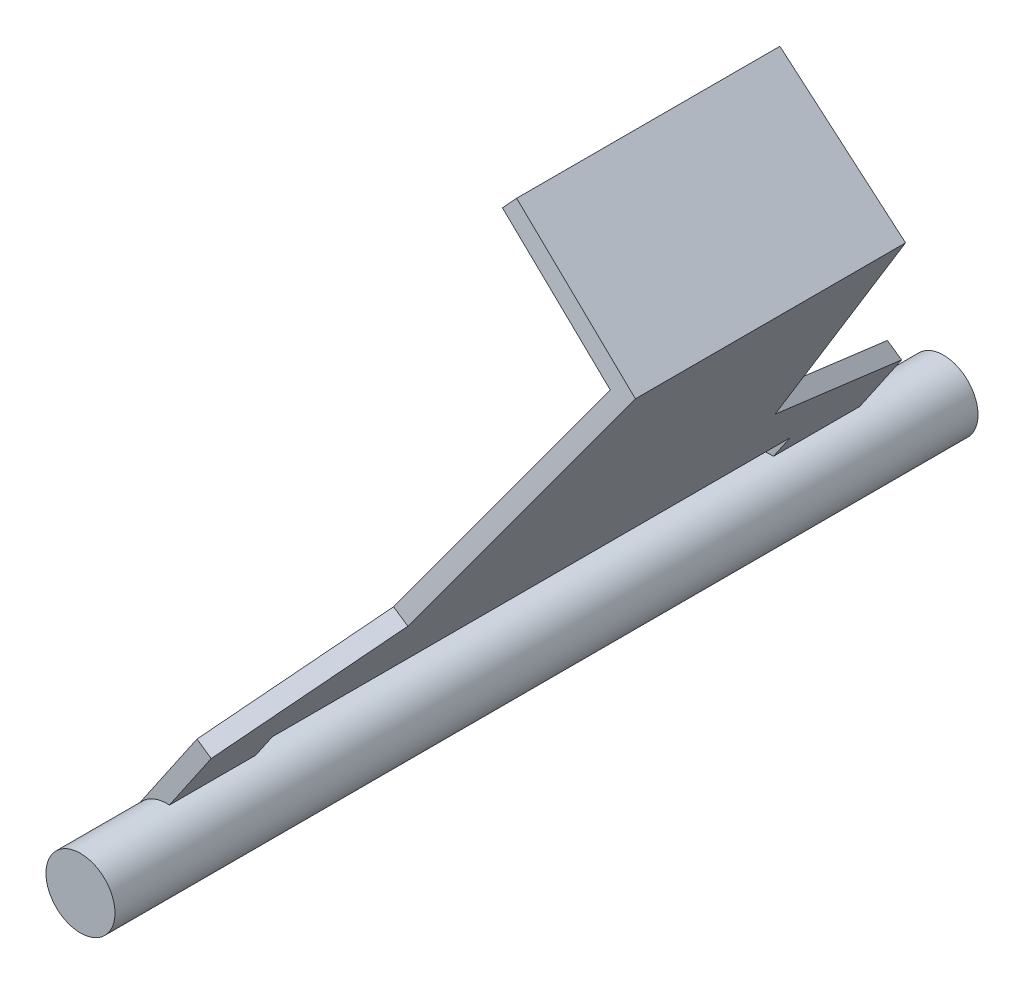
SolidWorks part; units mm, degrees
ref_plane "前视基准面" through (0, 0, 0) normal (0, 0, 1) x (1, 0, 0)
ref_plane "上视基准面" through (0, 0, 0) normal (0, 1, 0) x (1, 0, 0)
ref_plane "右视基准面" through (0, 0, 0) normal (1, 0, 0) x (0, 0, -1)
sketch "草图1" plane through (0, 0, 0) normal (0, 0, 1) x (1, 0, 0)
  line L0 (-3.3033, 2.2558) -> (27.3198, 47.099)
  line L1 (27.3198, 47.099) -> (14.4498, 58.7751)
  line L2 (0.3019, 3.9886) -> (29.9538, 47.4097)
  line L3 (29.9538, 47.4097) -> (15.7937, 60.2564)
  line L4 (15.7937, 60.2564) -> (14.4498, 58.7751)
  line L5 (-1.6516, 1.1279) -> (29.9538, 47.4097) construction
  circle A0 centre (0, 0) radius 4
  dimension "D1" = 54.3018
  dimension "D2" = 17.3772
  dimension "D3" = 2
  dimension "D4" = 2
extrude "凸台-拉伸1" add sketch "草图1" along normal mid plane 100 contours A0 region at (0, 0, 0)
extrude "凸台-拉伸2" add sketch "草图1<4>" along normal mid plane 80 contours A0 L2 L3 L4 L1 L0 region at (12.5604, 24.3003, 0)
sketch "草图1<4>" plane through (0, 0, 0) normal (0, 0, 1) x (1, 0, 0) same geometry as "草图1"
sketch "草图2" plane through (-1.6516, 1.1279, 0) normal (0.8258, -0.5639, 0) x (0, 0, -1)
  line L0 (0, 0) -> (0, 69.2101) construction
  line L1 (-14.6739, 62.4502) -> (-21.2689, 19.2529)
  line L2 (-21.2689, 19.2529) -> (-48.1385, 8.9338)
  line L3 (21.2689, 19.2529) -> (48.1385, 8.9338)
  line L4 (14.6739, 62.4502) -> (21.2689, 19.2529)
  line L5 (-48.1385, 8.9338) -> (-50.0561, 74.3696)
  line L6 (-50.0561, 74.3696) -> (58.321, 74.3696)
  line L7 (58.321, 74.3696) -> (48.1385, 8.9338)
  line L8 (-14.6739, 62.4502) -> (14.6739, 62.4502)
  dimension "D1" = 69.2101
  dimension "D2" = 43.6978
  dimension "D3" = 28.783
  dimension "D4" = 65.4638
  dimension "D5" = 108.3772
  dimension "D6" = 66.2233
  dimension "D7" = 29.3478
extrude "切除-拉伸1" cut sketch "草图2" against normal blind 80
sketch "草图3" plane through (0, 0, 0) normal (0, 0, 1) x (1, 0, 0)
  line L0 (2.2333, 6.8168) -> (-2.0182, 9.7201)
  line L1 (0.3019, 3.9886) -> (5.1492, 11.0867) construction
  line L2 (-2.0182, 9.7201) -> (-6.2415, 3.5356)
  circle A0 centre (0, 0) radius 4
  arc A1 (-5.5646, 4.5268) -> (2.2333, 6.8168) centre (0, 0) ccw
  dimension "D1" = 5.1482
  dimension "D2" = 7.4891
extrude "切除-拉伸2" cut sketch "草图3" against normal mid plane 60 contours L2 A1 L0 A0 region at (2.51, -6.4828, 0)
